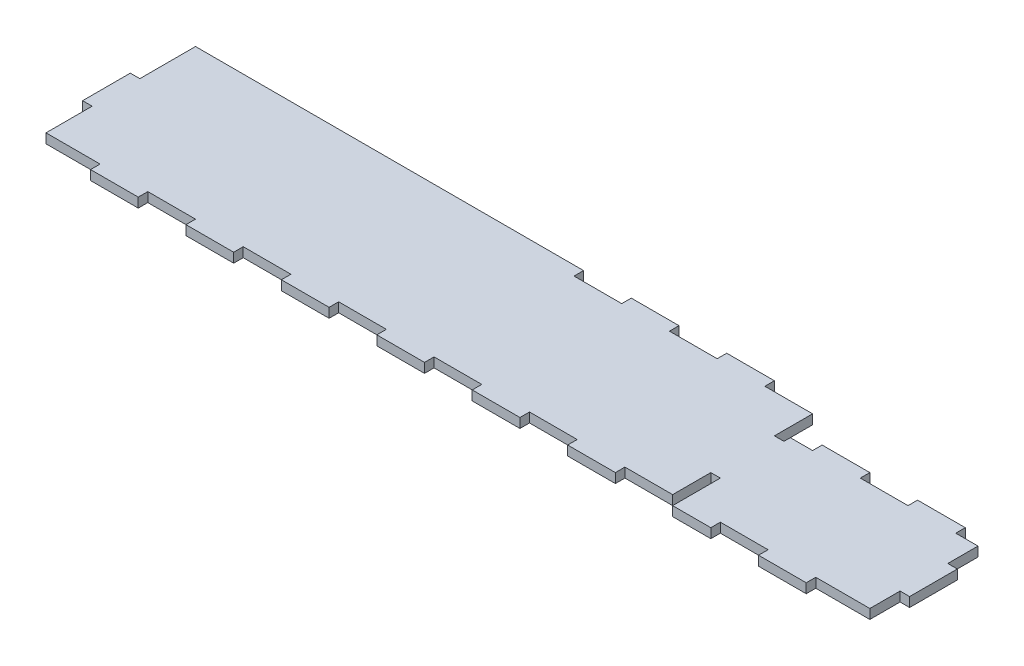
SolidWorks part; units mm, degrees
ref_plane "Alzado" through (0, 0, 0) normal (0, 0, 1) x (1, 0, 0)
ref_plane "Planta" through (0, 0, 0) normal (0, 1, 0) x (1, 0, 0)
ref_plane "Vista lateral" through (0, 0, 0) normal (1, 0, 0) x (0, 0, -1)
sketch "Croquis1" plane through (0, 0, 0) normal (0, 1, 0) x (1, 0, 0)
  line L0 (125, 50) -> (3, 50)
  line L1 (20, 50) -> (35, 50)
  line L2 (197, 3) -> (200, 3)
  line L3 (20, 0) -> (35, 0)
  line L4 (265, 12.5) -> (265, 27.5)
  line L5 (255, 40) -> (240, 40)
  line L6 (0, 25) -> (0, 32.5)
  line L7 (0, 32.5) -> (3, 32.5)
  line L8 (3, 32.5) -> (3, 47)
  line L9 (200, 15) -> (203, 15)
  line L10 (110, 47) -> (95, 47) construction
  line L11 (95, 47) -> (95, 50) construction
  line L12 (95, 50) -> (80, 50)
  line L13 (80, 50) -> (80, 47) construction
  line L14 (80, 47) -> (65, 47) construction
  line L15 (65, 47) -> (65, 50) construction
  line L16 (65, 50) -> (50, 50)
  line L17 (50, 50) -> (50, 47) construction
  line L18 (50, 47) -> (35, 47) construction
  line L19 (35, 47) -> (35, 50) construction
  line L20 (35, 50) -> (20, 50)
  line L21 (20, 50) -> (20, 47) construction
  line L22 (20, 47) -> (3, 47) construction
  line L23 (185, 47) -> (196.5, 47)
  line L24 (185, 50) -> (185, 47)
  line L25 (170, 47) -> (170, 50)
  line L26 (155, 47) -> (170, 47)
  line L27 (155, 50) -> (155, 47)
  line L28 (140, 47) -> (140, 50)
  line L29 (125, 47) -> (140, 47)
  line L30 (125, 50) -> (125, 47)
  line L31 (110, 47) -> (110, 50) construction
  line L32 (0, 25) -> (0, 17.5)
  line L33 (203, 15) -> (203, 0)
  line L34 (0, 17.5) -> (3, 17.5)
  line L35 (3, 17.5) -> (3, 3)
  line L36 (225, 40) -> (210, 40)
  line L37 (140, 3) -> (125, 3)
  line L38 (125, 3) -> (125, 0)
  line L39 (125, 0) -> (110, 0)
  line L40 (110, 0) -> (110, 3)
  line L41 (110, 3) -> (95, 3)
  line L42 (95, 3) -> (95, 0)
  line L43 (95, 0) -> (80, 0)
  line L44 (80, 0) -> (80, 3)
  line L45 (80, 3) -> (65, 3)
  line L46 (65, 3) -> (65, 0)
  line L47 (65, 0) -> (50, 0)
  line L48 (50, 0) -> (50, 3)
  line L49 (50, 3) -> (35, 3)
  line L50 (35, 3) -> (35, 0)
  line L51 (35, 0) -> (20, 0)
  line L52 (20, 0) -> (20, 3)
  line L53 (20, 3) -> (3, 3)
  line L54 (245, 3) -> (262, 3)
  line L55 (245, 0) -> (245, 3)
  line L56 (230, 3) -> (230, 0)
  line L57 (215, 3) -> (230, 3)
  line L58 (215, 0) -> (215, 3)
  line L59 (3, 50) -> (3, 47)
  line L60 (185, 3) -> (197, 3)
  line L61 (185, 0) -> (185, 3)
  line L62 (170, 3) -> (170, 0)
  line L63 (155, 3) -> (170, 3)
  line L64 (155, 0) -> (155, 3)
  line L65 (140, 3) -> (140, 0)
  line L66 (255, 40) -> (240, 40)
  line L67 (200, 35) -> (203, 35)
  line L68 (225, 37) -> (240, 37)
  line L69 (240, 37) -> (240, 40)
  line L70 (240, 40) -> (255, 40)
  line L71 (255, 40) -> (255, 37)
  line L72 (255, 37) -> (262, 37)
  line L73 (210, 37) -> (203, 37)
  line L74 (210, 40) -> (210, 37)
  line L75 (225, 37) -> (225, 40)
  line L76 (203, 35) -> (203, 37)
  line L78 (265, 20) -> (265, 27.5)
  line L79 (265, 27.5) -> (262, 27.5)
  line L80 (262, 27.5) -> (262, 37)
  line L81 (265, 20) -> (265, 12.5)
  line L82 (265, 12.5) -> (262, 12.5)
  line L83 (262, 12.5) -> (262, 3)
  line L85 (196.5, 47) -> (200, 47)
  line L87 (200, 35) -> (200, 37)
  line L89 (200, 15) -> (200, 3)
  line L90 (0, 17.5) -> (0, 32.5)
  line L91 (50, 0) -> (65, 0)
  line L92 (80, 0) -> (95, 0)
  line L93 (110, 0) -> (125, 0)
  line L94 (140, 0) -> (155, 0)
  line L95 (170, 0) -> (185, 0)
  line L96 (203, 0) -> (215, 0)
  line L97 (230, 0) -> (245, 0)
  line L98 (170, 50) -> (185, 50)
  line L99 (140, 50) -> (155, 50)
  line L100 (50, 50) -> (65, 50)
  line L101 (80, 50) -> (95, 50)
  line L102 (110, 50) -> (125, 50)
  line L103 (200, 47) -> (200, 37)
  point P42 (1.8266, -29.9859)
  dimension "D3" = 17
  dimension "D4" = 3
  dimension "D5" = 7.5
  dimension "D6" = 3
  dimension "D7" = 11.5
  dimension "D8" = 15
  dimension "D9" = 15
  dimension "D10" = 15
  dimension "D11" = 15
  dimension "D12" = 15
  dimension "D13" = 15
  dimension "D14" = 7.5
  dimension "D15" = 15
  dimension "D16" = 3
  dimension "D17" = 15
  dimension "D18" = 15
  dimension "D19" = 15
  dimension "D20" = 15
  dimension "D21" = 15
  dimension "D22" = 15
  dimension "D23" = 15
  dimension "D24" = 2
  dimension "D25" = 7
  dimension "D26" = 15
  dimension "D27" = 7.5
  dimension "D28" = 3
  dimension "D29" = 7.5
  dimension "D30" = 3
  dimension "D31" = 3
  dimension "D32" = 3
  dimension "D33" = 15
  dimension "D34" = 15
  dimension "D35" = 15
  dimension "D36" = 15
  dimension "D37" = 12
  dimension "D38" = 3
  dimension "D39" = 12
  dimension "D40" = 15
  dimension "D41" = 15
  dimension "D42" = 17
  dimension "D43" = 3
  dimension "D44" = 3
  dimension "D45" = 3
  dimension "D46" = 17
  dimension "D47" = 3
  dimension "D48" = 3
  dimension "D49" = 12
  dimension "D50" = 3
  dimension "D51" = 3
  dimension "D52" = 3
  dimension "D53" = 3
extrude "Saliente-Extruir1" add sketch "Croquis1" along normal blind 3 contours L102 L31 L10 L11 L12 L13 L14 L15 L16 L17 L18 L19 L1 L21 L22 L8 L7 L6 L32 L34 L35 L53 L52 L3 L50 L49 L48 L47 L46 L45 L44 L43 L42 L41 L40 L39 L38 L37 L65 L94 L64 L63 L62 L95 L61 L60 L89 L96 region at (125.8487, 0, -24.4393)
